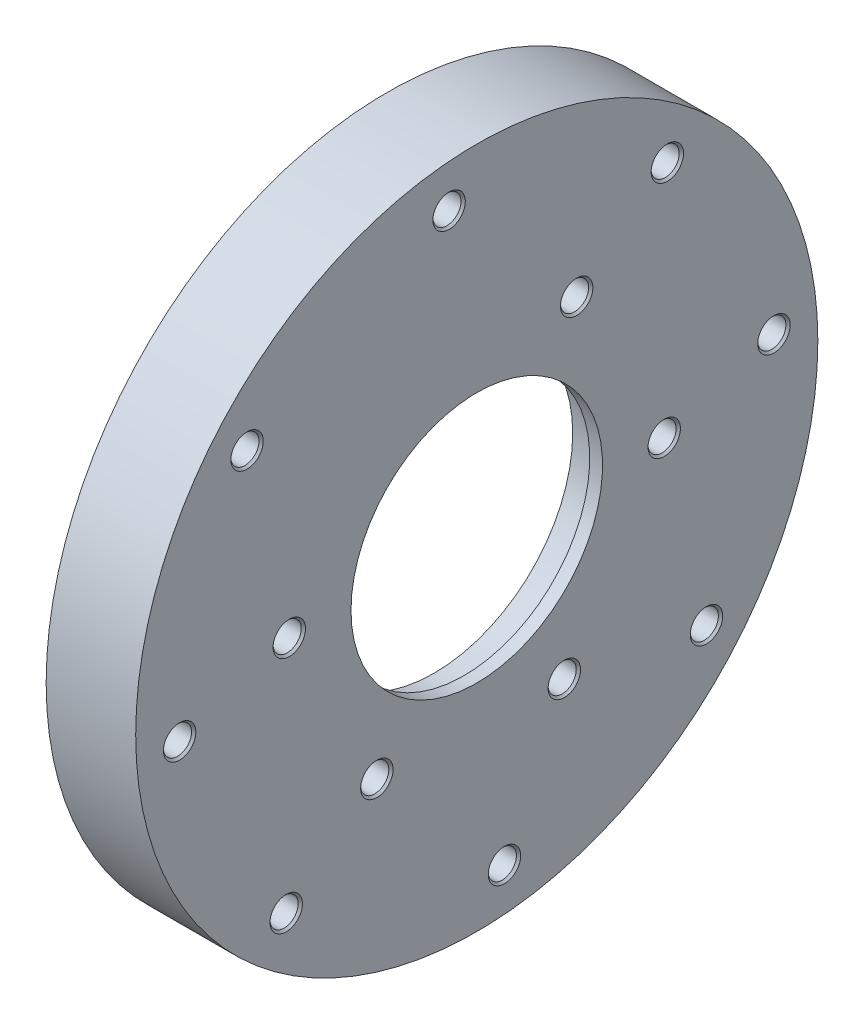
SolidWorks part; units mm, degrees
ref_plane "Front Plane" through (0, 0, 0) normal (0, 0, 1) x (1, 0, 0)
ref_plane "Top Plane" through (0, 0, 0) normal (0, 1, 0) x (1, 0, 0)
ref_plane "Right Plane" through (0, 0, 0) normal (1, 0, 0) x (0, 0, -1)
sketch "Sketch2" plane through (0, 0, 0) normal (0, 0, 1) x (1, 0, 0)
  line L0 (0, 0) -> (80.4799, 0) construction
  line L1 (0, 80) -> (0, 52.5)
  line L2 (0, 52.5) -> (11, 52.5)
  line L3 (11, 52.5) -> (11, 32.5)
  line L4 (11, 32.5) -> (18, 32.5)
  line L5 (18, 32.5) -> (18, 29.5)
  line L6 (18, 29.5) -> (21, 29.5)
  line L7 (21, 29.5) -> (21, 80)
  line L8 (21, 80) -> (0, 80)
  dimension "D1" = 80
  dimension "D2" = 32.5
  dimension "D3" = 52.5
  dimension "D4" = 18
  dimension "D5" = 3
  dimension "D6" = 7
  dimension "D7" = 3
revolve "Revolve1" add sketch "Sketch2" angle 360 about L0
sketch "Sketch3" plane through (0, 0, 0) normal (-1, 0, 0) x (0, 0, 1)
  circle A0 centre (0, 0) radius 60 construction
  circle A1 centre (0, 60) radius 2.51
  circle A2 centre (12.0779, 58.7718) radius 2.51
  circle A3 centre (23.6614, 55.1375) radius 2.51
  circle A4 centre (34.2761, 49.2458) radius 2.51
  circle A5 centre (43.4876, 41.338) radius 2.51
  circle A6 centre (50.9187, 31.7378) radius 2.51
  circle A7 centre (56.2651, 20.8383) radius 2.51
  circle A8 centre (59.3081, 9.0857) radius 2.51
  circle A9 centre (59.923, -3.039) radius 2.51
  circle A10 centre (58.0846, -15.0392) radius 2.51
  circle A11 centre (53.8683, -26.4236) radius 2.51
  circle A12 centre (47.4465, -36.7264) radius 2.51
  circle A13 centre (39.0823, -45.5255) radius 2.51
  circle A14 centre (29.1181, -52.4608) radius 2.51
  circle A15 centre (17.9618, -57.2484) radius 2.51
  circle A16 centre (6.0701, -59.6922) radius 2.51
  circle A17 centre (-6.0701, -59.6922) radius 2.51
  circle A18 centre (-17.9618, -57.2484) radius 2.51
  circle A19 centre (-29.1181, -52.4608) radius 2.51
  circle A20 centre (-39.0823, -45.5255) radius 2.51
  circle A21 centre (-47.4465, -36.7264) radius 2.51
  circle A22 centre (-53.8683, -26.4236) radius 2.51
  circle A23 centre (-58.0846, -15.0392) radius 2.51
  circle A24 centre (-59.923, -3.039) radius 2.51
  circle A25 centre (-59.3081, 9.0857) radius 2.51
  circle A26 centre (-56.2651, 20.8383) radius 2.51
  circle A27 centre (-50.9187, 31.7378) radius 2.51
  circle A28 centre (-43.4876, 41.338) radius 2.51
  circle A29 centre (-34.2761, 49.2458) radius 2.51
  circle A30 centre (-23.6614, 55.1375) radius 2.51
  circle A31 centre (-12.0779, 58.7718) radius 2.51
  point P67 (0, 0)
  dimension "D1" = 120
  dimension "D2" = 5.02
  dimension "D3" = 31
extrude "Cut-Extrude1" cut sketch "Sketch3" against normal blind 4
sketch "Sketch4" [suppressed] plane through (21, 0, 0) normal (1, 0, 0) x (0, 0, -1)
  circle A0 centre (-38.0255, -58.7712) radius 5.5
  circle A1 centre (-68.4457, -14.6694) radius 5.5
  circle A2 centre (-58.7712, 38.0255) radius 5.5
  circle A3 centre (-14.6694, 68.4457) radius 5.5
  circle A4 centre (38.0255, 58.7712) radius 5.5
  circle A5 centre (68.4457, 14.6694) radius 5.5
  circle A6 centre (58.7712, -38.0255) radius 5.5
  circle A7 centre (14.6694, -68.4457) radius 5.5
  point P16 (0, 0)
  dimension "D2" = 11
  dimension "D1" = 8
extrude "Cut-Extrude2" [suppressed] cut sketch "Sketch4" against normal blind 4
sketch "Sketch5" [suppressed] plane through (21, 0, 0) normal (1, 0, 0) x (0, 0, -1)
  circle A0 centre (-38.0255, -58.7712) radius 3
  circle A1 centre (-68.4457, -14.6694) radius 3
  circle A2 centre (-58.7712, 38.0255) radius 3
  circle A3 centre (-14.6694, 68.4457) radius 3
  circle A4 centre (38.0255, 58.7712) radius 3
  circle A5 centre (68.4457, 14.6694) radius 3
  circle A6 centre (58.7712, -38.0255) radius 3
  circle A7 centre (14.6694, -68.4457) radius 3
  point P16 (0, 0)
  dimension "D2" = 6
  dimension "D1" = 8
extrude "Cut-Extrude3" [suppressed] cut sketch "Sketch5" against normal through all
sketch "Sketch6" plane through (0, 0, 0) normal (-1, 0, 0) x (0, 0, 1)
  circle A0 centre (53.8756, 44.6925) radius 3
  circle A1 centre (69.6982, -6.4934) radius 3
  circle A2 centre (44.6925, -53.8756) radius 3
  circle A3 centre (-6.4934, -69.6982) radius 3
  circle A4 centre (-53.8756, -44.6925) radius 3
  circle A5 centre (-69.6982, 6.4934) radius 3
  circle A6 centre (-44.6925, 53.8756) radius 3
  circle A7 centre (6.4934, 69.6982) radius 3
  point P15 (0, 0)
  dimension "D2" = 6
  dimension "D1" = 8
extrude "Cut-Extrude4" cut sketch "Sketch6" against normal blind 11
sketch "Sketch7" plane through (21, 0, 0) normal (-1, 0, 0) x (0, 0, 1)
  circle A0 centre (53.8756, 44.6925) radius 3.3
  circle A1 centre (69.6982, -6.4934) radius 3.3
  circle A2 centre (44.6925, -53.8756) radius 3.3
  circle A3 centre (-6.4934, -69.6982) radius 3.3
  circle A4 centre (-53.8756, -44.6925) radius 3.3
  circle A5 centre (-69.6982, 6.4934) radius 3.3
  circle A6 centre (-44.6925, 53.8756) radius 3.3
  circle A7 centre (6.4934, 69.6982) radius 3.3
  point P15 (0, 0)
  dimension "D1" = 6.6
  dimension "D2" = 8
extrude "Cut-Extrude5" cut sketch "Sketch7" along normal blind 10
sketch "Sketch8" [suppressed] plane through (21, 0, 0) normal (1, 0, 0) x (0, 0, -1)
  circle A0 centre (-23.7966, 67.4351) radius 1
  dimension "D1" = 2
extrude "Cut-Extrude6" [suppressed] cut sketch "Sketch8" against normal blind 2
sketch "Sketch9" plane through (0, 0, 0) normal (-1, 0, 0) x (0, 0, 1)
  circle A0 centre (2.5177, -71.4663) radius 1
  dimension "D1" = 2
extrude "Cut-Extrude7" cut sketch "Sketch9" against normal blind 2
sketch "Sketch10" plane through (21, 0, 0) normal (1, 0, 0) x (0, 0, -1)
  line L0 (69.6982, 6.4934) -> (-44.6925, -53.8756) construction
  line L1 (23.4319, 37.2417) -> (0, 0) construction
  line L2 (0, 0) -> (43.9682, -1.6717) construction
  line L3 (0, 0) -> (-23.4319, -37.2417) construction
  circle A0 centre (0, 0) radius 44 construction
  circle A1 centre (23.4319, 37.2417) radius 3.3
  circle A2 centre (20.5363, -38.9135) radius 3.3
  circle A3 centre (-43.9682, 1.6717) radius 3.3
  circle A4 centre (-23.4319, -37.2417) radius 3.3
  circle A5 centre (43.9682, -1.6717) radius 3.3
  point P15 (0, 0)
  dimension "D1" = 6.6
  dimension "D2" = 88
  dimension "D3" = 30
  dimension "D5" = 60
  dimension "D6" = 120
  dimension "D4" = 3
extrude "Cut-Extrude8" cut sketch "Sketch10" against normal up to next
chamfer "Chamfer1" distance 0.5 angle 45 13 edges at (21, -53.8756, 47.9925) (21, -69.6982, -3.1934) (21, -44.6925, -50.5756) (21, 6.4934, -66.3982) (21, 44.6925, 57.1756) (21, -6.4934, 72.9982) (21, 1.6717, 40.6682) (21, -38.9135, -23.8363) (21, 37.2417, -26.7319) (21, -37.2417, 20.1319) (21, -1.6717, -47.2682) (21, 69.6982, 9.7934) (21, 53.8756, -41.3925)
equation "\"R_ROLL\"= 5mm"
equation "\"D_SUN\"= 120mm"
equation "\"NUM_ROLL\"= 31"
equation "\"RHO\"= 1mm"
equation "\"D_SHAFT\"= 28mm"
equation "\"D_OUTPUT\"= 80mm"
equation "\"NUM_OUT\"= 8"
equation "\"R_OUT_ROLL\"= 5mm"
equation "\"D1@Sketch3\"=\"D_SUN\""
